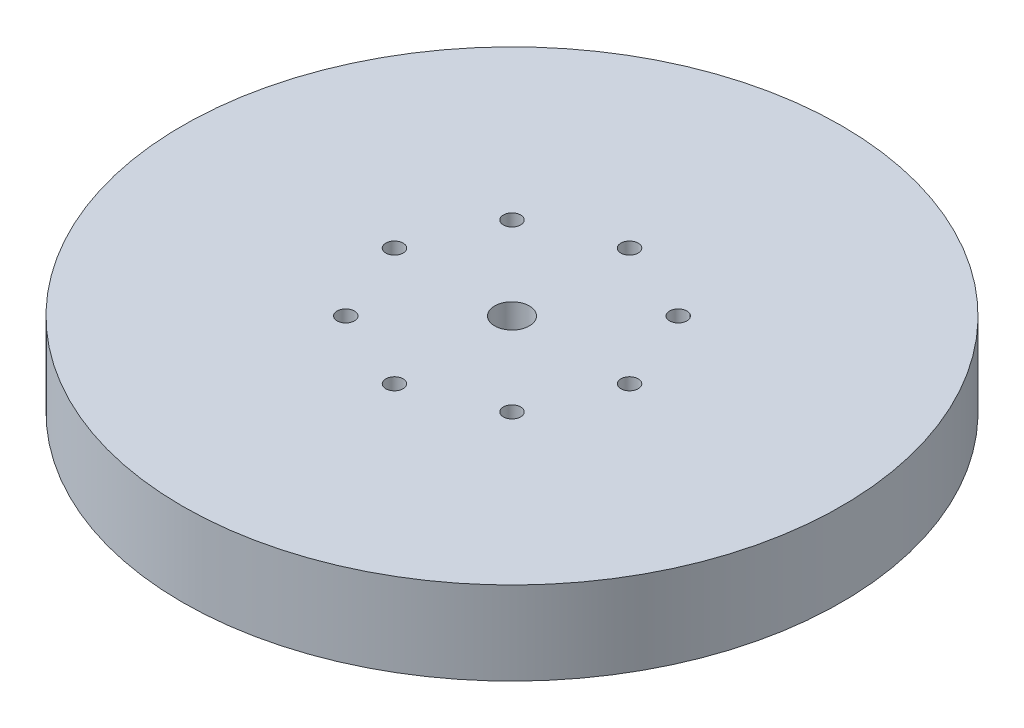
SolidWorks part; units mm, degrees
ref_plane "Front Plane" through (0, 0, 0) normal (0, 0, 1) x (1, 0, 0)
ref_plane "Top Plane" through (0, 0, 0) normal (0, 1, 0) x (1, 0, 0)
ref_plane "Right Plane" through (0, 0, 0) normal (1, 0, 0) x (0, 0, -1)
sketch "Sketch1" plane through (0, 0, 0) normal (0, 1, 0) x (1, 0, 0)
  circle A0 centre (0, 0) radius 95
  dimension "FLANGE_OD" = 190
extrude "Boss-Extrude1" add sketch "Sketch1" along normal blind 24
sketch "Sketch2" plane through (0, 0, 0) normal (0, 1, 0) x (1, 0, 0)
  circle A0 centre (0, 0) radius 5
  dimension "BORE_D" = 10
extrude "Cut-Extrude1" cut sketch "Sketch2" along normal through all
sketch "Sketch3" plane through (0, 24, 0) normal (0, 1, 0) x (1, 0, 0)
  circle A0 centre (0, 0) radius 33.8818 construction
  circle A1 centre (-33.8818, 0) radius 2.4967
  dimension "BOLT_D" = 4.9933
  dimension "BOLT_PCD" = 67.7636
extrude "Cut-Extrude2" cut sketch "Sketch3" against normal blind 21.1333
pattern_circular "CirPattern1" count 8 over 360 about axis through (0, 0, 0) along (0, 1, 0) of "Cut-Extrude2"
